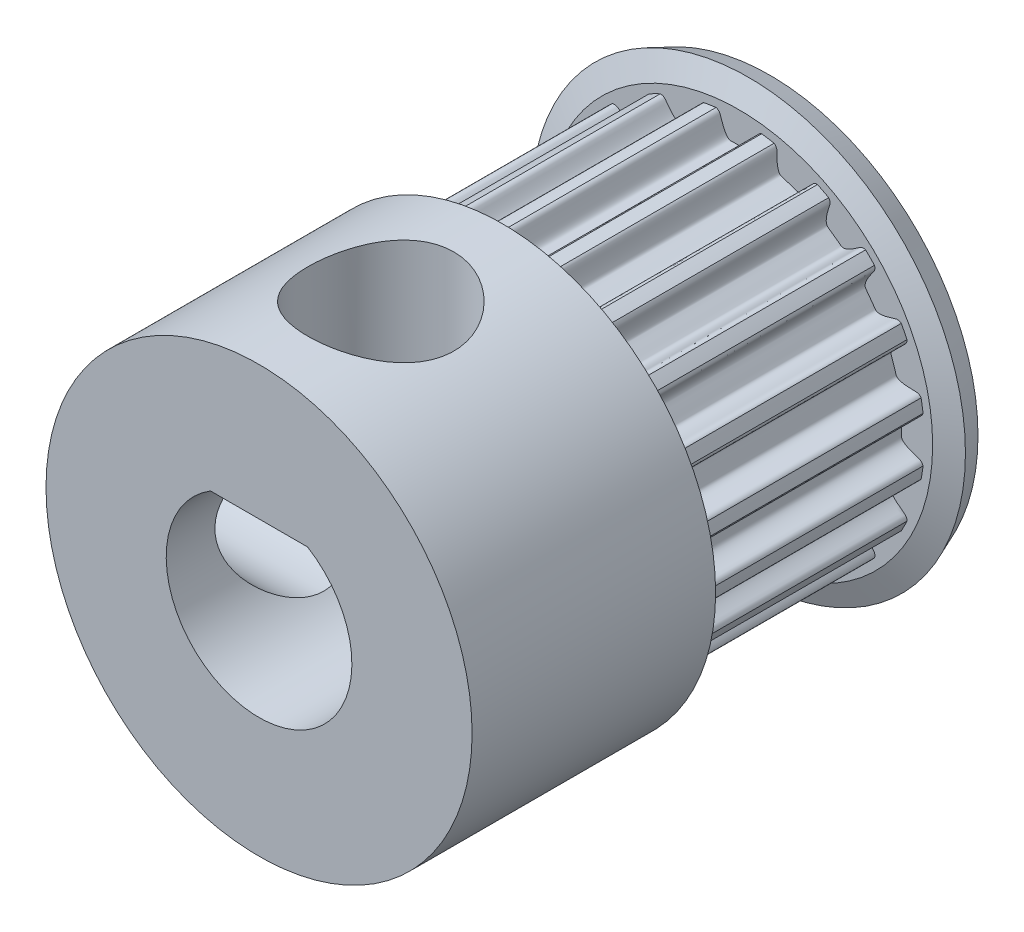
SolidWorks part; units mm, degrees
ref_plane "前视基准面" through (0, 0, 0) normal (0, 0, 1) x (1, 0, 0)
ref_plane "上视基准面" through (0, 0, 0) normal (0, 1, 0) x (1, 0, 0)
ref_plane "右视基准面" through (0, 0, 0) normal (1, 0, 0) x (0, 0, -1)
other "Configuration Table"
ref_axis "基准轴1" through (0, 0, 55) along (0, 0, -1)
sketch "SketchRevolveGearBelt01" plane through (0, 0, 0) normal (1, 0, 0) x (0, 0, -1)
  line L0 (0, 0) -> (1, 0) construction
  line L1 (5.274, 0) -> (5.274, 4.8662)
  line L2 (5.274, 4.8662) -> (4.512, 4.8662)
  line L3 (4.512, 4.8662) -> (4.512, 6.2146)
  line L4 (4.512, 6.2146) -> (4.7696, 6.8366)
  line L5 (4.7696, 6.8366) -> (4.0656, 7.1282)
  line L6 (4.0656, 7.1282) -> (3.75, 6.3662)
  line L7 (3.75, 6.3662) -> (3.75, 6.0974)
  line L8 (3.75, 6.0974) -> (-3.75, 6.0974)
  line L9 (-3.75, 6.0974) -> (-3.75, 6.3662)
  line L10 (-3.75, 6.3662) -> (-4.0656, 7.1282)
  line L11 (-4.0656, 7.1282) -> (-4.7696, 6.8366)
  line L12 (-4.7696, 6.8366) -> (-4.512, 6.2146)
  line L13 (-4.512, 6.2146) -> (-4.512, 4.8662)
  line L14 (-4.512, 4.8662) -> (-5.274, 4.8662)
  line L15 (-5.274, 4.8662) -> (-5.274, 0)
  line L16 (-5.274, 0) -> (5.274, 0)
  dimension "GearBeltFlange1OutsideLength" = 1.3484
  dimension "GearBeltFlange1X" = 0.2576
  dimension "GearBeltFlange1Y" = 0.622
  dimension "GearBeltFlangeThickness" = 0.762
  dimension "GearBeltFlangeInside" = 0.2688
  dimension "GearBeltOutsideDiameter" = 6.0974
  dimension "GearBeltFlange2X" = 0.2576
revolve "Gates_PowerGrip_GT_2mm, 6mm Belt Width" add sketch "SketchRevolveGearBelt01" angle 360 about L0
sketch "SketchToothGearBelt01" plane through (0, 0, 0) normal (0, 0, 1) x (1, 0, 0)
  arc A0 (6.0575, 0.8121) -> (6.0575, -0.8121) centre (0, 0) cw
  spline S0 degree 3 poles (6.0575, -0.8121) (6.0583, -0.7986) (6.0575, -0.7783) (6.0524, -0.7518) (6.0465, -0.7324) (6.0388, -0.7137) (6.0292, -0.6958) (6.0178, -0.6791) (6.0048, -0.6635) (5.9903, -0.6494) (5.9744, -0.6368) (5.9573, -0.6259) (5.9393, -0.6166) (5.9014, -0.6028) (5.8513, -0.5872) (5.7909, -0.5675) (5.7401, -0.5498) (5.6924, -0.5322) (5.6478, -0.5145) (5.6062, -0.4969) (5.5678, -0.4793) (5.5323, -0.4616) (5.5, -0.444) (5.4707, -0.4264) (5.4445, -0.4087) (5.4213, -0.3911) (5.4012, -0.3734) (5.3842, -0.3558) (5.3702, -0.3381) (5.3592, -0.3203) (5.3514, -0.3025) (5.3465, -0.2846) (5.3443, -0.2503) (5.3481, -0.2) (5.3485, -0.1333) (5.3495, -0.0666) (5.3497, 0) (5.3495, 0.0666) (5.3485, 0.1333) (5.3481, 0.2) (5.3443, 0.2503) (5.3465, 0.2846) (5.3514, 0.3025) (5.3592, 0.3203) (5.3702, 0.3381) (5.3842, 0.3558) (5.4012, 0.3734) (5.4213, 0.3911) (5.4445, 0.4087) (5.4707, 0.4264) (5.5, 0.444) (5.5323, 0.4616) (5.5678, 0.4793) (5.6062, 0.4969) (5.6478, 0.5145) (5.6924, 0.5322) (5.7401, 0.5498) (5.7909, 0.5675) (5.8513, 0.5872) (5.9014, 0.6028) (5.9393, 0.6166) (5.9573, 0.6259) (5.9744, 0.6368) (5.9903, 0.6494) (6.0048, 0.6635) (6.0178, 0.6791) (6.0292, 0.6958) (6.0388, 0.7137) (6.0465, 0.7324) (6.0524, 0.7518) (6.0575, 0.7783) (6.0583, 0.7986) (6.0575, 0.8121) knots 0 0 0 0 0.016481 0.024721 0.032961 0.041201 0.049442 0.057682 0.065922 0.074162 0.082403 0.090643 0.098883 0.107123 0.13988 0.162959 0.184851 0.205564 0.225106 0.24349 0.260727 0.276834 0.291831 0.305741 0.318596 0.330433 0.341302 0.351266 0.360409 0.368837 0.376686 0.384125 0.391349 0.41855 0.4457 0.47285 0.5 0.52715 0.5543 0.58145 0.608651 0.615875 0.623314 0.631163 0.639591 0.648734 0.658698 0.669567 0.681404 0.694259 0.708169 0.723166 0.739273 0.75651 0.774894 0.794436 0.815149 0.837041 0.86012 0.892877 0.901117 0.909357 0.917597 0.925838 0.934078 0.942318 0.950558 0.958799 0.967039 0.975279 0.983519 1 1 1 1
extrude "ToothExtrudeCutGearBelt01" cut sketch "SketchToothGearBelt01" against normal blind 3.75 and the other way blind 3.75
pattern_circular "Tooth Pattern, 20" count 20 every 18 about axis through (0, 0, 55) along (0, 0, -1) of "ToothExtrudeCutGearBelt01"
sketch "BoreRevolveSketch" plane through (0, 0, 0) normal (1, 0, 0) x (0, 0, -1)
  line L0 (0, 0) -> (1, 0) construction
  line L1 (-5.274, 0) -> (5.274, 0)
  line L2 (5.274, 0) -> (5.274, 5)
  line L3 (5.274, 5) -> (-5.274, 5)
  line L4 (-5.274, 5) -> (-5.274, 0)
  dimension "TaperSide1" = 5
  dimension "TaperSide2" = 5
revolve "BoreRevolveCut" cut sketch "BoreRevolveSketch" angle 360 about L0
sketch "AuxiliarySketchGearBelt01" plane through (0, 0, 0) normal (0, 0, 1) x (1, 0, 0)
  circle A0 centre (0, 0) radius 6.3662 construction
  dimension "PitchDiameter" = 12.7324
sketch "草图6" plane through (0, 0, 4.512) normal (0, 0, 1) x (1, 0, 0)
  circle A0 centre (0, 0) radius 7.1282
extrude "切除-拉伸2" cut sketch "草图6" along normal through all
sketch "草图7" plane through (0, 0, 4.512) normal (0, 0, 1) x (1, 0, 0)
  circle A0 centre (0, 0) radius 7.1282
extrude "切除-拉伸3" cut sketch "草图7" against normal blind 0.5
sketch "草图8" plane through (0, 0, 4.012) normal (0, 0, 1) x (1, 0, 0)
  circle A0 centre (0, 0) radius 6.9987
extrude "凸台-拉伸2" add sketch "草图8" along normal blind 8
sketch "草图9" plane through (0, 0, 4.012) normal (0, 0, -1) x (-1, 0, 0)
  circle A0 centre (0, 0) radius 5
extrude "凸台-拉伸3" add sketch "草图9" along normal blind 8.5
sketch "草图10" plane through (0, 0, -4.488) normal (0, 0, -1) x (-1, 0, 0)
  circle A0 centre (0, 0) radius 3.05
  dimension "D1" = 6.1
extrude "切除-拉伸4" cut sketch "草图10" against normal through all
sketch "草图11" plane through (0, 0, 12.012) normal (0, 0, 1) x (1, 0, 0)
  line L0 (0, 0) -> (0, 2.6)
  line L1 (-1000, 2.6) -> (49000, 2.6)
  circle A0 centre (0, 0) radius 2.6
  circle A1 centre (0, 0) radius 3.05
  circle M1 centre (0, 0) radius 3.05
  dimension "D1" = 5.2
extrude "凸台-拉伸4" add sketch "草图11" against normal blind 16.5 contours L1 M1 region at (0, 2.7812, 12.012)
sketch "草图12" plane through (0, 2.6, 0) normal (0, -1, 0) x (1, 0, 0)
  line L0 (0, 12.012) -> (0, 8.012)
  line L1 (3.05, 12.012) -> (-3.05, 12.012) construction
  line L2 (0, 55) -> (0, -55) construction
  circle A0 centre (0, 8.012) radius 2.4
  line M3 (-1.5945, 12.012) -> (-1.5945, -4.488)
  line M5 (1.5945, -4.488) -> (1.5945, 12.012)
  dimension "D2" = 4.8
  dimension "D1" = 4
extrude "切除-拉伸6" cut sketch "草图12" against normal mid plane 9 contours A0 M3 | A0 M5 | A0 M5 M3 region at (1.9218, 2.6, 8.012) region at (1.5369, 2.6, 8.012) region at (-1.9218, 2.6, 8.012)
sketch "草图13" plane through (0, 0, 0) normal (1, 0, 0) x (0, 0, -1)
  line L0 (-12.012, 0) -> (-8.012, 0)
  line L1 (-12.012, 6.9987) -> (-12.012, -6.9987) construction
  line L2 (-55, 0) -> (55, 0) construction
  circle A0 centre (-8.012, 0) radius 2.4
  dimension "D2" = 4.8
  dimension "D1" = 4
extrude "切除-拉伸7" cut sketch "草图13" against normal through all contours A0 region at (0, -2.3321, 8.012)
